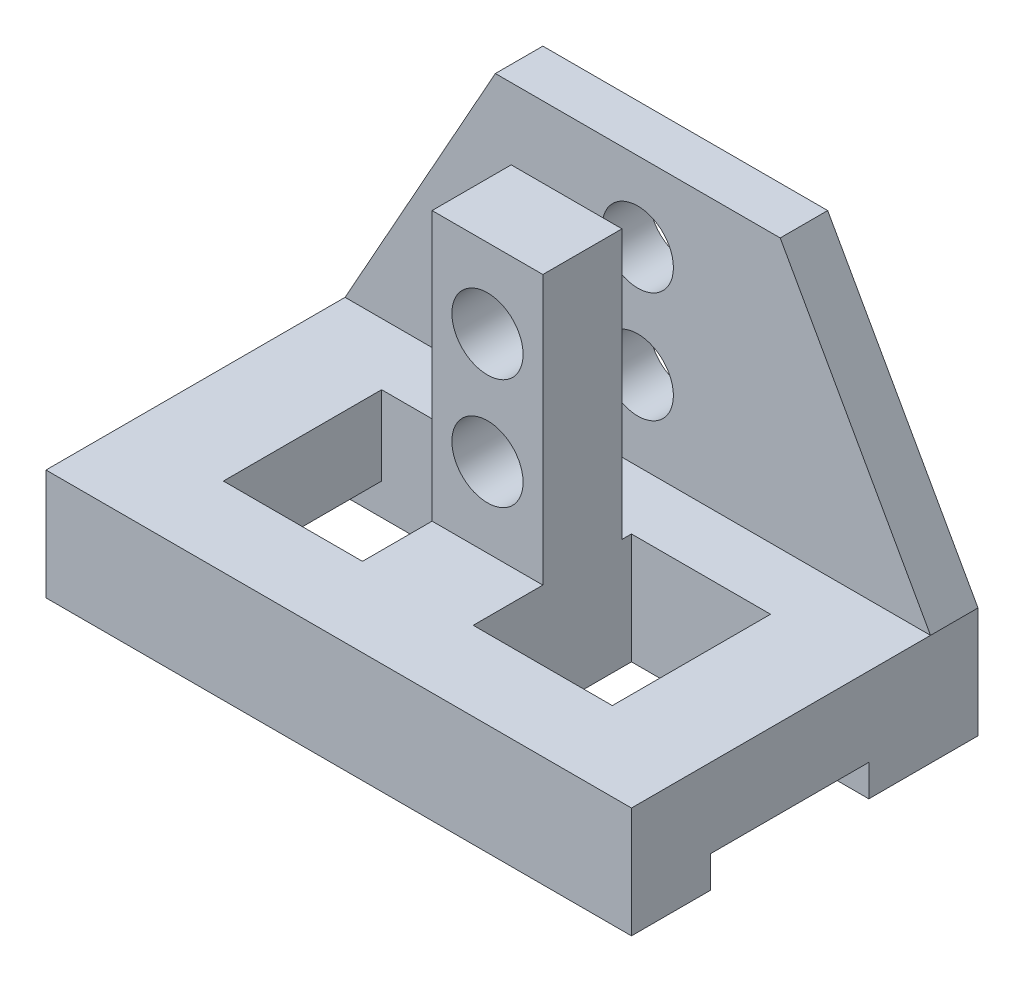
SolidWorks part; units mm, degrees
ref_plane "Plan de face" through (0, 0, 0) normal (0, 0, 1) x (1, 0, 0)
ref_plane "Plan de dessus" through (0, 0, 0) normal (0, 1, 0) x (1, 0, 0)
ref_plane "Plan de droite" through (0, 0, 0) normal (1, 0, 0) x (0, 0, -1)
sketch "Esquisse1" plane through (0, 0, 0) normal (0, 0, 1) x (1, 0, 0)
  line L0 (0, 17) -> (20, 17)
  line L1 (0, 0) -> (20, 0)
  line L2 (0, 0) -> (0, 25.6902)
  line L3 (0, 25.6902) -> (20, 25.6902)
  line L4 (20, 0) -> (20, 25.6902)
  circle A0 centre (10, 5) radius 2.1
  circle A1 centre (10, 12) radius 2.1
  dimension "D2" = 4.2
  dimension "D3" = 4.2
  dimension "D1" = 20
  dimension "D5" = 10
  dimension "D6" = 5
  dimension "D7" = 7
  dimension "D9" = 17
  dimension "D11" = 10
extrude "Boss.-Extru.1" add sketch "Esquisse1" along normal blind 5 contours L1 L4 L0 L2 A1 A0 region at (10, 8.5, 0)
sketch "Esquisse2" plane through (0, 0, 0) normal (0, -1, 0) x (1, 0, 0)
  line L0 (20, 5) -> (20, 0) construction
  line L1 (0, 0) -> (20, 0)
  line L2 (0, 0) -> (0, 5)
  line L3 (0, 5) -> (20, 5)
  line L4 (20, 0) -> (20, 5)
  line L5 (1, 5) -> (1, 0)
  line L6 (19, 5) -> (19, 0)
  line L7 (1, 3) -> (19, 3)
  line L9 (1, 0) -> (19, 0)
  line L10 (1, 0) -> (1, -5)
  line L11 (1, -5) -> (19, -5)
  line L12 (19, 0) -> (19, -5)
  line L13 (1, 0) -> (19, 0)
  line L14 (1, 0) -> (1, -0.6)
  line L15 (1, -0.6) -> (19, -0.6)
  line L16 (19, 0) -> (19, -0.6)
  point P11 (19, 2.5)
  dimension "D1" = 5
  dimension "D2" = 18
  dimension "D3" = 1
  dimension "D4" = 3
  dimension "D5" = 5
  dimension "D6" = 0.6
extrude "Boss.-Extru.3" add sketch "Esquisse2" along normal blind 5 contours L15 L10 L11 L12 region at (10, 0, -2.8)
sketch "Esquisse5" plane through (0, 0, 5) normal (0, 0, 1) x (1, 0, 0)
  line L0 (13.5, 17) -> (13.5, 0)
  line L1 (0, 17) -> (20, 17) construction
  line L2 (0, 0) -> (20, 0) construction
  line L3 (13.5, 0) -> (20, 0)
  line L4 (20, 0) -> (20, 17)
  line L5 (20, 0) -> (20, 17) construction
  line L6 (20, 17) -> (13.5, 17)
  line L8 (0, 0) -> (6.5, 0)
  line L9 (0, 0) -> (0, 17)
  line L10 (0, 17) -> (6.5, 17)
  line L11 (6.5, 0) -> (6.5, 17)
  dimension "D1" = 6.5
  dimension "D2" = 6.5
extrude "Enlèv. mat.-Extru.3" cut sketch "Esquisse5" against normal blind 18
sketch "Esquisse10" plane through (0, 0, 5) normal (0, 0, 1) x (1, 0, 0)
  line L1 (6.5, 0) -> (13.5, 0)
  line L2 (6.5, 0) -> (6.5, -7)
  line L3 (6.5, -7) -> (13.5, -7)
  line L4 (13.5, 0) -> (13.5, -7)
  dimension "D1" = 7
  dimension "D2" = 7
extrude "Boss.-Extru.6" add sketch "Esquisse10" against normal blind 10 and the other way blind 9.4
sketch "Esquisse11" plane through (0, 0, 0) normal (0, 1, 0) x (1, 0, 0)
  line L0 (6.5, 0.6) -> (6.5, 0) construction
  line L1 (6.5, 0) -> (13.5, 0)
  line L2 (6.5, 0) -> (6.5, 5)
  line L3 (6.5, 5) -> (13.5, 5)
  line L4 (13.5, 0) -> (13.5, 5)
  line L5 (6.5, 0) -> (13.5, 0) construction
  line L6 (1, 5) -> (19, 5) construction
  line L8 (13.5, 4.5) -> (6.5, 4.5)
  line L9 (13.5, 4.5) -> (13.5, 0)
  line L10 (13.5, 0) -> (6.5, 0)
  line L11 (6.5, 4.5) -> (6.5, 0)
  line L12 (6.5, 4.5) -> (13.5, 4.5)
  line L13 (6.5, 4.5) -> (6.5, 7.5)
  line L14 (6.5, 7.5) -> (13.5, 7.5)
  line L15 (13.5, 4.5) -> (13.5, 7.5)
  line L16 (6.5, 4.5) -> (1, 4.5)
  line L17 (6.5, 4.5) -> (6.5, 7.5)
  line L18 (6.5, 7.5) -> (1, 7.5)
  line L19 (1, 4.5) -> (1, 7.5)
  line L20 (13.5, 4.5) -> (19, 4.5)
  line L21 (13.5, 4.5) -> (13.5, 7.5)
  line L22 (13.5, 7.5) -> (19, 7.5)
  line L23 (19, 4.5) -> (19, 7.5)
  line M12 (19, 0.6) -> (19, 5)
  line M13 (19, 5) -> (1, 5)
  line M14 (1, 5) -> (1, 0.6)
  dimension "D1" = 7
  dimension "D2" = 4.5
  dimension "D3" = 3
  dimension "D4" = 5.5
  dimension "D5" = 5.5
extrude "Boss.-Extru.7" add sketch "Esquisse11" along normal blind 17 contours L19 L13 L18 M13 | L15 L14 L13 M13 | L23 L22 L15 M13 | L16 L2 M13 M14 | L8 L4 L2 M13 | L4 L20 M12 M13 region at (3.75, 0, -4.75) region at (10, 0, -4.75) region at (16.25, 0, -4.75) region at (10, 0, -6.25) region at (3.75, 0, -6.25) region at (16.25, 0, -6.25)
sketch "Esquisse12" plane through (0, 0, 0) normal (0, -1, 0) x (1, 0, 0)
  line L5 (1, -5) -> (19, -5)
  line L6 (1, -5) -> (1, -7.5)
  line L7 (1, -7.5) -> (19, -7.5)
  line L8 (19, -5) -> (19, -7.5)
extrude "Boss.-Extru.8" add sketch "Esquisse12" along normal blind 7
sketch "Esquisse20" plane through (0, 0, 5) normal (0, 0, 1) x (1, 0, 0)
  circle A0 centre (10, 5) radius 2.25
  circle A1 centre (10, 12) radius 2.25
  dimension "D1" = 4.5
extrude "Enlèv. mat.-Extru.7" cut sketch "Esquisse20" against normal blind 18
sketch "Esquisse21" plane through (13.5, 0, 0) normal (1, 0, 0) x (0, 0, -1)
  line L0 (-14.4, -7) -> (5, -7) construction
  line L1 (-14.4, 0) -> (-9.4, 0)
  line L2 (-14.4, 0) -> (-14.4, -7)
  line L3 (-14.4, -7) -> (-9.4, -7)
  line L4 (-9.4, 0) -> (-9.4, -7)
  line L7 (0.6, 0) -> (7.5, 0)
  line L8 (0.6, 0) -> (0.6, -7)
  line L9 (0.6, -7) -> (7.5, -7)
  line L11 (7.5, 0) -> (7.5, -7)
  dimension "D1" = 5
  dimension "D2" = 6.9
extrude "Boss.-Extru.9" add sketch "Esquisse21" along normal blind 15
sketch "Esquisse22" plane through (0, 0, -0.6) normal (0, 0, 1) x (1, 0, 0)
  line L0 (1, -5) -> (6.5, -5) construction
  line L1 (28.5, 0) -> (22.2897, 0)
  line L2 (28.5, 0) -> (28.5, -5)
  line L3 (28.5, -5) -> (22.2897, -5)
  line L4 (22.2897, 0) -> (22.2897, -5)
extrude "Boss.-Extru.10" add sketch "Esquisse22" along normal up to surface (15 mm away) up to face at (17.5, -3.5, 14.4)
sketch "Esquisse24" plane through (0, 0, -7.5) normal (0, 0, -1) x (-1, 0, 0)
  line L0 (-28.5, 0) -> (-19, 0)
  line L2 (-19, 0) -> (-19, 17)
  line L5 (-19, 17) -> (-28.5, 0)
extrude "Boss.-Extru.11" add sketch "Esquisse24" against normal up to surface (3 mm away) up to face at (12.25, 12, -4.5)
ref_plane "Plan1" through (10, 0, 0) normal (-1, 0, 0) x (0, 0, 1)
mirror "Symétrie1" about plane through (10, 0, 0) normal (-1, 0, 0) of "Boss.-Extru.11", "Boss.-Extru.10", "Boss.-Extru.9"
